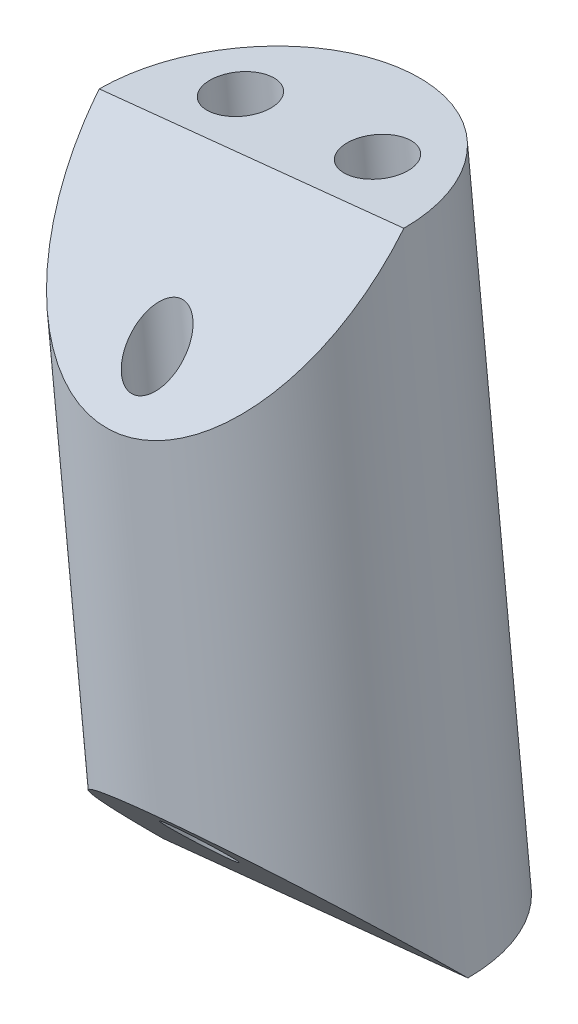
SolidWorks part; units mm, degrees
ref_plane "Front Plane" through (0, 0, 0) normal (0, 0, 1) x (1, 0, 0)
ref_plane "Top Plane" through (0, 0, 0) normal (0, 1, 0) x (1, 0, 0)
ref_plane "Right Plane" through (0, 0, 0) normal (1, 0, 0) x (0, 0, -1)
sketch "Sketch2" plane through (0, 0, 0) normal (0, 0, 1) x (1, 0, 0)
  line L0 (0, 0) -> (90, 0)
  line L1 (90, 0) -> (90, 120)
  line L2 (90, 120) -> (0, 120)
  line L3 (0, 120) -> (0, 0)
  line L4 (0, 120) -> (-10, 120)
  line L5 (-10, 120) -> (-10, 16.9491)
  line L6 (-10, 120) -> (57.5, 127)
  line L7 (57.5, 127) -> (90, 124)
  line L8 (90, 120) -> (99, 60)
  line L10 (90, 124) -> (90, 120)
  line L11 (5.9147, 0) -> (5.9147, -25)
  line L12 (5.9147, -25) -> (-4.0853, -25)
  line L13 (-4.0853, -29) -> (-4.0853, 0)
  line L14 (80, 0) -> (80, -25)
  line L15 (80, -25) -> (90, -25)
  line L16 (90, -29) -> (90, 0)
  line L17 (15.7927, 122.6748) -> (5.4776, 222.1414)
  line L18 (5.4776, 222.1414) -> (21.3923, 223.7918)
  line L19 (21.3923, 223.7918) -> (31.7073, 124.3252)
  line L20 (7.6492, 201.201) -> (23.5639, 202.8514)
  line L21 (10.9066, 169.7905) -> (26.8212, 171.441)
  line L22 (-10, 120) -> (-20.0396, 216.8108)
  line L23 (-20.0396, 216.8108) -> (-4.125, 218.4612)
  line L24 (-4.125, 218.4612) -> (5.9147, 121.6504)
  line L25 (-17.926, 196.4296) -> (-2.0114, 198.08)
  line L26 (-14.7556, 165.8578) -> (1.159, 167.5082)
  line L27 (57.5, 127) -> (46.9095, 229.1223)
  line L28 (46.9095, 229.1223) -> (30.9949, 227.4719)
  line L29 (30.9949, 227.4719) -> (41.5853, 125.3496)
  line L30 (33.2245, 205.9725) -> (49.1391, 207.6229)
  line L31 (36.5688, 173.7233) -> (52.4835, 175.3737)
  line L34 (90, 124) -> (99.1917, 223.5767)
  line L35 (99.1917, 223.5767) -> (83.2594, 225.0473)
  line L36 (83.2594, 225.0473) -> (74.0677, 125.4707)
  line L38 (81.3243, 204.0838) -> (97.2566, 202.6132)
  line L39 (78.4217, 172.6386) -> (94.354, 171.1679)
  line L40 (62.4078, 79.6749) -> (57.5, 127) construction
  line L41 (41.5853, 125.3496) -> (46.4931, 78.0244) construction
  line L42 (46.4931, 78.0244) -> (62.4078, 79.6749) construction
  line L43 (31.7073, 124.3252) -> (36.6151, 77.0001) construction
  line L44 (36.6151, 77.0001) -> (20.7005, 75.3496) construction
  line L45 (20.7005, 75.3496) -> (15.7927, 122.6748) construction
  line L46 (5.9147, 121.6504) -> (10.8224, 74.3253) construction
  line L47 (10.8224, 74.3253) -> (-5.0922, 72.6749) construction
  line L48 (-5.0922, 72.6749) -> (-10, 120) construction
  line L49 (74.0677, 125.4707) -> (69.6944, 78.0931) construction
  line L50 (69.6944, 78.0931) -> (85.7624, 78.0931) construction
  line L51 (85.7624, 78.0931) -> (90, 124) construction
  line L52 (-12.0823, 217.636) -> (10.4873, 0) construction
  line L53 (13.4349, 222.9666) -> (36.5574, 0) construction
  line L54 (38.9522, 228.2971) -> (62.6275, 0) construction
  line L55 (91.2256, 224.312) -> (70.5198, 0) construction
  line L59 (99, 60) -> (93.5277, 44.9649)
  line L60 (99, 60) -> (169.4769, 34.3485)
  line L61 (169.4769, 34.3485) -> (164.0046, 19.3134)
  line L62 (164.0046, 19.3134) -> (93.5277, 44.9649)
  line L63 (90, -2) -> (100, -2)
  line L64 (141.2862, 44.6091) -> (135.8138, 29.574)
  line L65 (99, 60) -> (55.7741, 75.7329) construction
  line L66 (55.7741, 75.7329) -> (50.3018, 60.6978) construction
  line L67 (100, -2) -> (100, -29)
  line L70 (-4.0853, -2) -> (-14.0853, -2)
  line L71 (-14.0853, -2) -> (-14.0853, -29)
  line L74 (-4.0853, 0) -> (0, 0)
  line L75 (-14.0853, -29) -> (-14.0853, -112.587)
  line L76 (-14.0853, -112.587) -> (100, -112.587)
  line L77 (100, -112.587) -> (100, -29)
  line L78 (-14.0853, -29) -> (100, -29)
  line L79 (-14.0853, -14.5) -> (100, -14.5) construction
  line L80 (31.7073, -112.587) -> (31.7073, -122.6232)
  line L81 (31.7073, -122.6232) -> (42.9573, -122.6232)
  line L82 (42.9573, -122.6232) -> (42.9573, -112.587)
  line L83 (-14.0853, -112.587) -> (-88.3667, -112.587)
  line L84 (-88.3667, -112.587) -> (-88.3667, -128.2699)
  line L85 (-88.3667, -128.2699) -> (169.4958, -128.2699)
  line L86 (169.4958, -128.2699) -> (169.4958, -112.587)
  line L87 (169.4958, -112.587) -> (100, -112.587)
  line L88 (90, 60) -> (-10, 60) construction
  line L89 (50.3018, 60.6978) -> (93.5277, 44.9649) construction
  line L90 (87.2806, 55.7521) -> (166.7408, 26.8309) construction
  line L91 (87.2806, 55.7521) -> (82.1749, 52.5336) construction
  line L92 (82.1749, 52.5336) -> (77.3257, 0) construction
  line L93 (83.1185, 56.6957) -> (86.337, 51.59) construction
  arc A0 (-10, 16.9491) -> (-4.0853, 0) centre (14.9876, 16.1624) ccw
  arc A1 (93.5277, 44.9649) -> (90, 0) centre (-126.4069, 39.5988) cw
  point P42 (41.1818, 206.7977)
  point P100 (84.7278, 54.1428)
  point P101 (84.7278, 54.1428)
  dimension "D11" = 47.3684
  dimension "D35" = 9
  dimension "D32" = 220
  dimension "D36" = 25
  dimension "D1" = 120
  dimension "D2" = 90
  dimension "D3" = 10
  dimension "D5" = 67.862
  dimension "D6" = 7
  dimension "D7" = 4
  dimension "D8" = 16
  dimension "D9" = 16
  dimension "D10" = 100
  dimension "D12" = 31.5789
  dimension "D13" = 16
  dimension "D14" = 16
  dimension "D15" = 16
  dimension "D16" = 25.7927
  dimension "D17" = 100
  dimension "D18" = 21.0526
  dimension "D19" = 31.5789
  dimension "D20" = 97.33
  dimension "D21" = 102.67
  dimension "D22" = 20.4905
  dimension "D23" = 30.7358
  dimension "D24" = 21.6147
  dimension "D25" = 32.4221
  dimension "D26" = 25
  dimension "D28" = 25
  dimension "D29" = 75
  dimension "D30" = 47.5789
  dimension "D31" = 30
  dimension "D33" = 46
  dimension "D34" = 20
  dimension "D37" = 2
  dimension "D38" = 2
  dimension "D39" = 27
  dimension "D40" = 10
  dimension "D41" = 10
  dimension "D42" = 27
  dimension "D43" = 14.5
  dimension "D44" = 127.5
ref_plane "Plane1" through (87.2806, 55.7521, 0) normal (-0.846, -0.5333, 0) x (0, 0, 1)
ref_plane "Plane2" through (82.1749, 52.5336, 0) normal (-0.0919, -0.9958, 0) x (-0.9958, 0.0919, 0)
ref_plane "Plane3" through (91.2256, 224.312, 0) normal (-0.0919, -0.9958, 0) x (-0.9958, 0.0919, 0)
ref_plane "Plane4" through (38.9522, 228.2971, 0) normal (0.1032, -0.9947, 0) x (-0.9947, -0.1032, 0)
ref_plane "Plane5" through (13.4349, 222.9666, 0) normal (0.1032, -0.9947, 0) x (-0.9947, -0.1032, 0)
ref_plane "Plane7" through (166.7408, 26.8309, 0) normal (0.9397, -0.342, 0) x (0, 0, -1)
ref_plane "Plane8" through (110.4217, -40.1902, 0) normal (0.9397, -0.342, 0) x (0, 0, -1)
ref_plane "Plane9" through (19.3664, 209.803, 0) normal (-0.0919, -0.9958, 0) x (-0.9958, 0.0919, 0)
ref_plane "Plane10" through (16.4638, 178.3578, 0) normal (-0.0919, -0.9958, 0) x (-0.9958, 0.0919, 0)
ref_plane "Plane11" through (-20.7793, 200.3721, 0) normal (0.1032, -0.9947, 0) x (-0.9947, -0.1032, 0)
ref_plane "Plane12" through (-17.435, 168.1229, 0) normal (0.1032, -0.9947, 0) x (-0.9947, -0.1032, 0)
ref_plane "Plane13" through (-20.5619, 198.2754, 0) normal (0.1032, -0.9947, 0) x (-0.9947, -0.1032, 0)
ref_plane "Plane14" through (-17.3045, 166.8649, 0) normal (0.1032, -0.9947, 0) x (-0.9947, -0.1032, 0)
ref_plane "Plane15" through (-12.0823, 217.636, 0) normal (0.1032, -0.9947, 0) x (-0.9947, -0.1032, 0)
ref_plane "Plane16" through (-20.3445, 196.1788, 0) normal (0.1032, -0.9947, 0) x (-0.9947, -0.1032, 0)
ref_plane "Plane17" through (-17.1741, 165.607, 0) normal (0.1032, -0.9947, 0) x (-0.9947, -0.1032, 0)
ref_plane "Plane18" through (12.1098, 131.1899, 0) normal (-0.0919, -0.9958, 0) x (-0.9958, 0.0919, 0)
ref_plane "Plane19" through (-12.4184, 119.7492, 0) normal (0.1032, -0.9947, 0) x (-0.9947, -0.1032, 0)
ref_plane "Plane20" through (0, 0, 0) normal (0, 0, 1) x (0.1032, -0.9947, 0)
ref_plane "Plane21" through (0, 0, 0) normal (0, 0, 1) x (-0.0919, -0.9958, 0)
ref_plane "Plane22" through (10.3758, 1.076, 0) normal (-0.9947, -0.1032, 0) x (0.1032, -0.9947, 0)
ref_plane "Plane23" through (36.1684, 3.7508, 0) normal (-0.9947, -0.1032, 0) x (0.1032, -0.9947, 0)
ref_plane "Plane24" through (61.9611, 6.4256, 0) normal (-0.9947, -0.1032, 0) x (0.1032, -0.9947, 0)
ref_plane "Plane25" through (69.924, -6.4545, 0) normal (-0.9958, 0.0919, 0) x (-0.0919, -0.9958, 0)
sketch "Sketch3" plane through (-20.3445, 196.1788, 0) normal (0.1032, -0.9947, 0) x (-0.9947, -0.1032, 0)
  line L0 (-2.4314, 0) -> (-18.4314, 0) construction
  circle A0 centre (-10.4314, 0) radius 8
  dimension "D1" = 16
extrude "Boss-Extrude1" add sketch "Sketch3" along normal blind 32.4221
sketch "Sketch4" plane through (10.3758, 1.076, 0) normal (-0.9947, -0.1032, 0) x (0.1032, -0.9947, 0)
  line L0 (-197.2309, 0) -> (-189.2309, 8)
  line L1 (-197.2309, 8) -> (-197.2309, -8) construction
  line L2 (-164.8088, 8) -> (-197.2309, 8) construction
  line L3 (-189.2309, 8) -> (-197.2309, 8)
  line L4 (-197.2309, 8) -> (-197.2309, 0)
  line L5 (-172.8088, 8) -> (-164.8088, 8)
  line L6 (-164.8088, 8) -> (-164.8088, 0)
  line L7 (-217.7214, 0) -> (1.0818, 0) construction
  line L8 (-164.8088, 0) -> (-172.8088, 8)
  dimension "D1" = 45
  dimension "D2" = 45
extrude "Cut-Extrude1" cut sketch "Sketch4" against normal through all and the other way through all
sketch "Sketch5" plane through (10.3758, 1.076, 0) normal (-0.9947, -0.1032, 0) x (0.1032, -0.9947, 0)
  line L0 (-164.8088, 0) -> (-168.8088, 4)
  line L1 (-164.8088, 0) -> (-172.8088, 8) construction
  line L2 (-168.8088, 4) -> (-160.8088, 4)
  line L3 (-160.8088, 4) -> (-160.8088, 0)
  line L4 (-213.7055, 0) -> (7.2742, 0) construction
  line L6 (-164.8088, 0) -> (-160.8088, 4) construction
  line L7 (-160.8088, 0) -> (-164.8088, -4)
  line L8 (-164.8088, -8) -> (-164.8088, 0) construction
  line L9 (-164.8088, 0) -> (-164.8088, -4)
  dimension "D1" = 4
  dimension "D2" = 45
sketch "Sketch7" plane through (10.3758, 1.076, 0) normal (-0.9947, -0.1032, 0) x (0.1032, -0.9947, 0)
  line L0 (-193.2309, 4) -> (-197.2309, 0)
  line L1 (-217.7214, 0) -> (1.0818, 0) construction
  line L4 (-197.2309, -4) -> (-197.2309, 0)
  line L5 (-193.2309, 4) -> (-193.2309, 0)
  arc A0 (-197.2309, -4) -> (-193.2309, 0) centre (-197.2309, 0) ccw
  dimension "D1" = 4
  dimension "D2" = 4
sketch "Sketch8" plane through (-20.3445, 196.1788, 0) normal (-0.1032, 0.9947, 0) x (0.9947, 0.1032, 0)
  line L0 (2.4314, 0) -> (18.4314, 0) construction
  circle A0 centre (10.4314, -5.5) radius 1.4
  circle A1 centre (6.8314, 3) radius 1.6
  circle A2 centre (14.0314, 3) radius 1.6
  point P9 (10.4314, 0)
  dimension "D1" = 3.2
  dimension "D2" = 3.2
  dimension "D3" = 2.8
  dimension "D4" = 3
  dimension "D5" = 5.5
  dimension "D6" = 3.6
  dimension "D7" = 3.6
  dimension "D8" = 3
extrude "Cut-Extrude3" cut sketch "Sketch8" against normal through all and the other way through all
sketch "Sketch9" plane through (-20.3445, 196.1788, 0) normal (-0.1032, 0.9947, 0) x (0.9947, 0.1032, 0)
  line L0 (4.5289, 5.4) -> (16.3339, 5.4)
  line L1 (-101.1265, 0) -> (155.3606, 0) construction
  arc A0 (18.4314, 0) -> (2.4314, 0) centre (10.4314, 0) ccw construction
  arc A1 (4.5289, 5.4) -> (16.3339, 5.4) centre (10.4314, 0) cw
  dimension "D1" = 5.4
